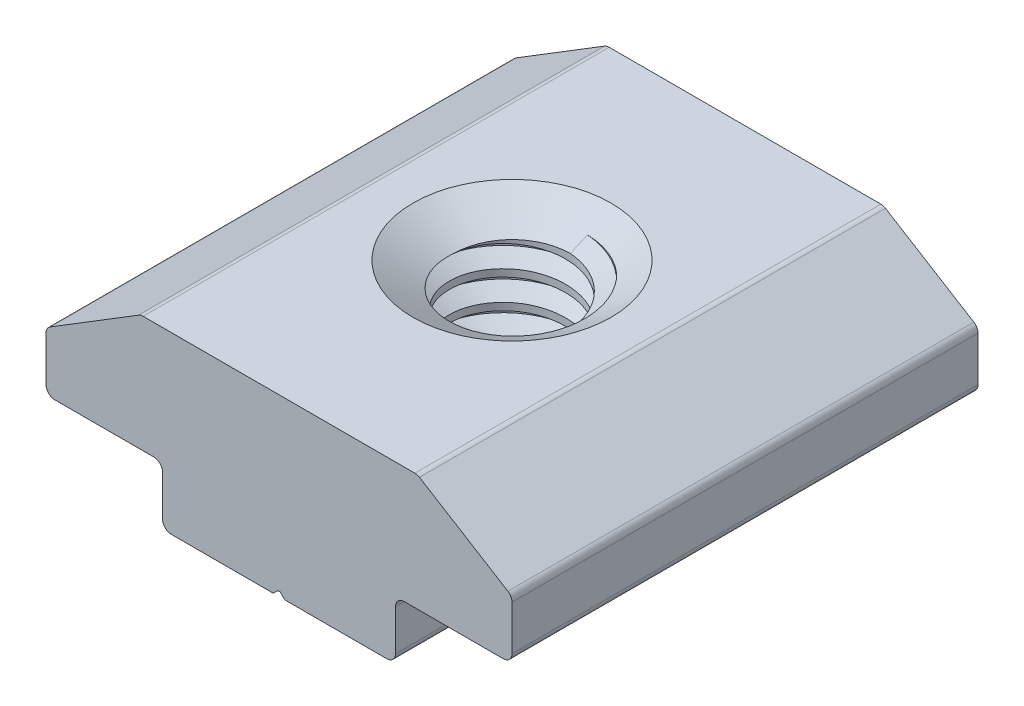
SolidWorks part; units mm, degrees
material "Простая углеродистая сталь"
ref_plane "Front" through (0, 0, 0) normal (0, 0, 1) x (1, 0, 0)
ref_plane "Top" through (0, 0, 0) normal (0, 1, 0) x (1, 0, 0)
ref_plane "Right" through (0, 0, 0) normal (1, 0, 0) x (0, 0, -1)
sketch "Эскиз1" plane through (0, 0, 0) normal (0, 0, 1) x (1, 0, 0)
  line L0 (0, 0) -> (0, 16710.1171) construction
  line L1 (-4, 0) -> (4, 0)
  line L2 (4, 0) -> (4, 2)
  line L3 (4, 2) -> (8, 2)
  line L4 (8, 2) -> (4.75, 6) construction
  line L5 (4.75, 6) -> (-4.75, 6)
  line L6 (-4.75, 6) -> (-8, 2) construction
  line L7 (-8, 2) -> (-4, 2)
  line L8 (-4, 2) -> (-4, 0)
  line L9 (-8, 2) -> (-8, 4)
  line L10 (-8, 4) -> (-4.75, 6)
  line L11 (8, 2) -> (8, 4)
  line L12 (8, 4) -> (4.75, 6)
  point P12 (0, 0)
  point P13 (0, 6)
  dimension "D1" = 6
  dimension "D2" = 16
  dimension "D3" = 9.5
  dimension "D4" = 4
  dimension "D5" = 2
  dimension "D6" = 8
  dimension "D7" = 2
extrude "Бобышка-Вытянуть1" add sketch "Эскиз1" along normal blind 16
sketch "Эскиз5" plane through (0, 6, 0) normal (0, 1, 0) x (1, 0, 0)
  line L0 (0, 0) -> (0, -50000) construction
  line L1 (-2.8, -8) -> (49997.2, -8) construction
  line L3 (-4, -16) -> (-4, 0) construction
  circle A0 centre (0, -8) radius 2
  point P12 (-4, -8)
  dimension "D1" = 4
extrude "Вырез-Вытянуть2" cut sketch "Эскиз5" against normal through all
sketch "Эскиз6" plane through (0, 0, 0) normal (1, 0, 0) x (0, 0, -1)
  line L0 (-16, 6) -> (0, 6) construction
  line L2 (-8, 5.7246) -> (-8, -49994.2754) construction
  line L3 (-5.4, 5.0203) -> (-5.4, -49994.9797) construction
  line L4 (-16, 0) -> (0, 0) construction
  line L6 (-8, 7.3875) -> (-5.4, 7.3875) construction
  line L7 (-6, 6.5) -> (-6, 5.2)
  line L8 (-6, 5.2) -> (-4.6, 6)
  line L9 (-4.6, 6) -> (-4.6, 6.5)
  line L10 (-4.6, 6.5) -> (-6, 6.5)
  line L11 (-6, 0.8) -> (-6, -0.8)
  line L12 (-6, -0.8) -> (-4.5, -0.8)
  line L13 (-4.5, -0.8) -> (-4.5, 0)
  line L14 (-16, 0) -> (0, 0) construction
  line L15 (-4.5, 0) -> (-6, 0.8)
  line L16 (-4.6, 6) -> (-4.6, -49994) construction
  point P28 (-8, 0)
  dimension "D1" = 2.6
  dimension "D2" = 0.8
  dimension "D3" = 0.1
  dimension "D4" = 0.8
  dimension "D5" = 0.8
  dimension "D6" = 0.5
  dimension "D7" = 0.8
  dimension "D8" = 1.5
  dimension "D9" = 1.4
fillet "Скругление1" radius 0.3 10 edges at (-4.75, 6, 8) (-8, 4, 8) (-8, 2, 8) (-4, 2, 8) (-4, 0, 8) (4, 0, 8) (4, 2, 8) (8, 2, 8) (8, 4, 8) (4.75, 6, 8)
sketch "Эскиз7" plane through (0, 0, 16) normal (0, 0, 1) x (1, 0, 0)
  line L0 (0, 0) -> (0, 50000) construction
  line L1 (0, 0.2) -> (-0.2, 0)
  line L2 (-3.7, 0) -> (3.7, 0) construction
  line L3 (-0.2, 0) -> (-0.2, -0.2)
  line L4 (-0.2, -0.2) -> (0.2, -0.2)
  line L5 (0.2, -0.2) -> (0.2, 0)
  line L6 (0.2, 0) -> (0, 0.2)
  dimension "D1" = 0.2
  dimension "D2" = 0.2
  dimension "D3" = 0.2
  dimension "D4" = 0.2
extrude "Вырез-Вытянуть3" cut sketch "Эскиз7" against normal through all
fillet "Скругление2" radius 0.1 6 edges at (-0.2, 0, 12.995) (0, 0.2, 13) (0.2, 0, 12.995) (0, 0.2, 3) (-0.2, 0, 3.005) (0.2, 0, 3.005)
revolve "Вырез-Повернуть1" cut sketch "Эскиз6" angle 360 about L2
thread "Резьба2" pitch 1 method cut trim with start face yes profile "Профиль резьбы2" start angle 0, offset 2, length 12, pitch 1, diameter 4
ref_plane "Плоскость2" through (-2, 7.2, 8) normal (0, 0, 1) x (-1, 0, 0)
sketch "Профиль резьбы2" plane through (-2, 7.2, 8) normal (0, 0, 1) x (-1, 0, 0)
  line L0 (0, 0) -> (0, 1) construction
  line L1 (0, 0) -> (0.5413, 0.3125)
  line L2 (0.5413, 0.3125) -> (0.5413, 0.4375)
  line L3 (0.5413, 0.4375) -> (0, 0.75)
  line L4 (0.5413, 0.375) -> (0, 0.375) construction
  line L11 (0, 0) -> (0, 0.75)
  point P2 (0, 0)
  dimension "Pitch" = 1
  dimension "Profile_Angle" = 60
  dimension "Profile_Land" = 0.125
  dimension "Profile_Height" = 0.5413
